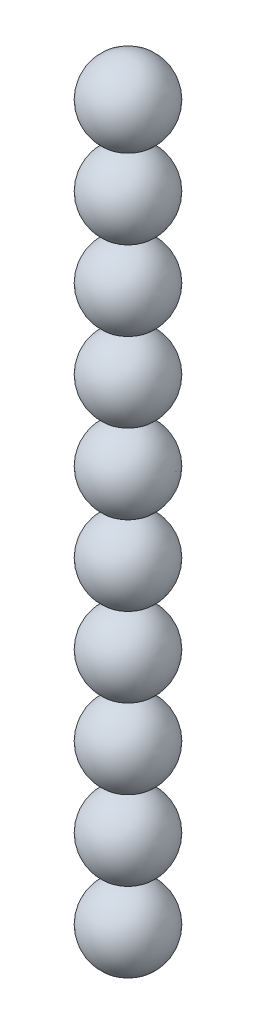
SolidWorks part; units mm, degrees
ref_plane "Front Plane" through (0, 0, 0) normal (0, 0, 1) x (1, 0, 0)
ref_plane "Top Plane" through (0, 0, 0) normal (0, 1, 0) x (1, 0, 0)
ref_plane "Right Plane" through (0, 0, 0) normal (1, 0, 0) x (0, 0, -1)
sketch "Sketch1" plane through (0, 0, 0) normal (0, 0, 1) x (1, 0, 0)
  line L0 (0, 3) -> (0, -3)
  line L1 (0, 9.254) -> (0, 3.254)
  line L2 (0, 15.508) -> (0, 9.508)
  line L3 (0, 21.762) -> (0, 15.762)
  line L4 (0, 28.016) -> (0, 22.016)
  line L5 (0, 34.27) -> (0, 28.27)
  line L6 (0, 40.524) -> (0, 34.524)
  line L7 (0, 46.778) -> (0, 40.778)
  line L8 (0, 53.032) -> (0, 47.032)
  line L9 (0, 59.286) -> (0, 53.286)
  arc A11 (0, 3) -> (0, -3) centre (0, 0) cw
  arc A12 (0, 9.254) -> (0, 3.254) centre (0, 6.254) cw
  arc A13 (0, 15.508) -> (0, 9.508) centre (0, 12.508) cw
  arc A14 (0, 21.762) -> (0, 15.762) centre (0, 18.762) cw
  arc A15 (0, 28.016) -> (0, 22.016) centre (0, 25.016) cw
  arc A16 (0, 34.27) -> (0, 28.27) centre (0, 31.27) cw
  arc A17 (0, 40.524) -> (0, 34.524) centre (0, 37.524) cw
  arc A18 (0, 46.778) -> (0, 40.778) centre (0, 43.778) cw
  arc A19 (0, 53.032) -> (0, 47.032) centre (0, 50.032) cw
  arc A20 (0, 59.286) -> (0, 53.286) centre (0, 56.286) cw
  point P5 (0, 0)
  dimension "D1" = 6
  dimension "D2" = 10
  dimension "D3" = 0.254
revolve "Revolve6" add sketch "Sketch1" angle 360 about L0
ref_axis "Axis1" through (0, -6.1143, 0) along (0, 1, 0)
